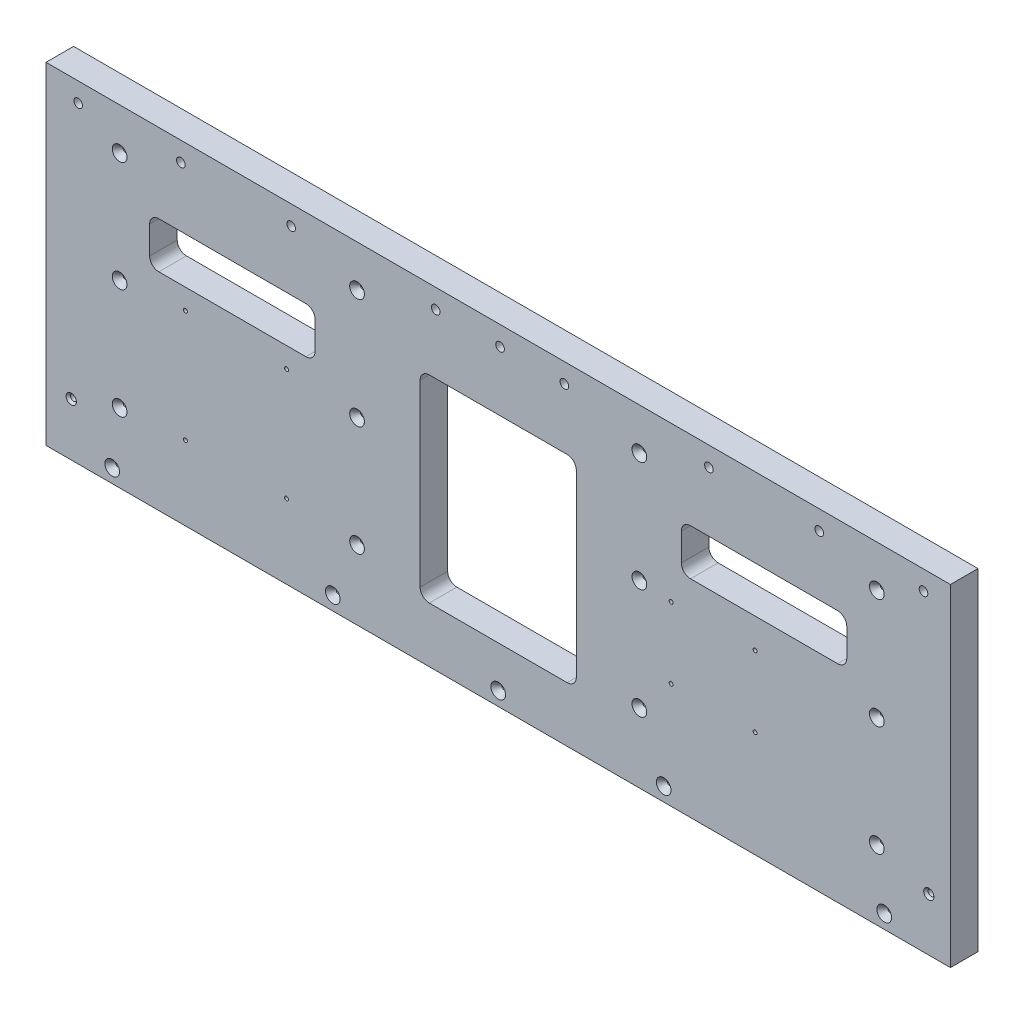
SolidWorks part; units mm, degrees
material "MDF"
ref_plane "Front Plane" through (0, 0, 0) normal (0, 0, 1) x (1, 0, 0)
ref_plane "Top Plane" through (0, 0, 0) normal (0, 1, 0) x (1, 0, 0)
ref_plane "Right Plane" through (0, 0, 0) normal (1, 0, 0) x (0, 0, -1)
sketch "Sketch1" plane through (0, 0, 0) normal (0, 0, 1) x (1, 0, 0)
  line L0 (128.7463, -697.8385) -> (128.7463, -158.115) construction
  line L1 (-496.0937, -132.715) -> (128.7463, -132.715)
  line L2 (-496.0937, -132.715) -> (-496.0937, -361.95)
  line L3 (-496.0937, -361.95) -> (128.7463, -361.95)
  line L4 (128.7463, -132.715) -> (128.7463, -361.95)
  line L5 (-496.0937, -132.715) -> (-496.0937, -697.8385) construction
  line L12 (128.7463, -132.715) -> (-84.6137, -132.715) construction
  line L13 (-290.722, -342.9) -> (-271.672, -342.9) construction
  dimension "D1" = 19.05
extrude "Boss-Extrude1" add sketch "Sketch1" along normal blind 19.05
hole_wizard "5/64 (0.07813) Diameter Hole1" positions "Sketch5" profile "Sketch6" hole size "5/64" standard "ANSI Inch"
sketch "Sketch5" plane through (-182.4037, -6471.4599, 19.05) normal (0, 0, 1) x (1, 0, 0)
  line L1 (-1.27, 6109.5099) -> (-1.27, 6338.7449) construction
  point P0 (-262.8265, 6157.4524)
  point P6 (-98.7933, 6157.4524)
  point P18 (-262.8265, 6233.6524)
  point P19 (-98.7933, 6233.6524)
  point P22 (-262.8265, 6309.8524)
  point P23 (-98.7933, 6309.8524)
  point P24 (-267.97, 6119.0349)
  point P34 (-115.57, 6119.0349)
  point P37 (-1.27, 6119.0349)
  point P40 (113.03, 6119.0349)
  point P44 (265.43, 6119.0349)
  point P55 (96.2533, 6309.8524)
  point P56 (260.2865, 6309.8524)
  point P59 (96.2533, 6233.6524)
  point P60 (260.2865, 6233.6524)
  point P63 (96.2533, 6157.4524)
  point P64 (260.2865, 6157.4524)
sketch "Sketch6" plane through (-445.2302, -314.0075, 19.05) normal (1, 0, 0) x (0, -1, 0)
  line L0 (0, 0) -> (0, 39.0539)
  line L1 (0, 39.0539) -> (1.5875, 38.1)
  line L2 (1.5875, 38.1) -> (1.5875, 4.0177)
  line L3 (1.5875, 4.0177) -> (5.08, 0)
  line L4 (5.08, 0) -> (0, 0)
  line L5 (-1.5875, 4.0177) -> (-5.08, 0) construction
  line L6 (0, 39.0539) -> (-1.5875, 38.1) construction
  line L7 (0, -6.35) -> (0, 107.95) construction
  dimension "Hole Dia." = 3.175
  dimension "Hole Depth" = 38.1
  dimension "Near C'Sink Dia." = 10.16
  dimension "Near C'Sink Angle" = 82
  dimension "Drill Angle" = 118
hole_wizard "15/64 (0.23438) Diameter Hole1" positions "Sketch7" profile "Sketch8" hole size "15/64" standard "ANSI Inch" end condition up to next
sketch "Sketch7" plane through (0, 0, 0) normal (0, 0, -1) x (-1, 0, 0)
  point P0 (402.9075, -146.05)
  point P2 (326.7075, -146.05)
  point P4 (226.8537, -146.05)
  point P6 (182.4037, -146.05)
  point P8 (137.9537, -146.05)
  point P10 (38.1, -146.05)
  point P12 (-38.1, -146.05)
  point P13 (473.8687, -146.05)
  point P17 (-110.1471, -146.05)
sketch "Sketch8" plane through (-402.9075, -146.05, 0) normal (1, 0, 0) x (0, 1, 0)
  line L0 (0, 0) -> (0, 19.05)
  line L1 (0, 19.05) -> (2.9766, 19.05)
  line L2 (2.9766, 19.05) -> (2.9766, 0)
  line L5 (2.9766, 0) -> (0, 0)
  line L11 (0, -6.35) -> (0, 107.95) construction
  dimension "Thru Hole Dia." = 5.9533
  dimension "Thru Hole Depth" = 19.05
sketch "Sketch9" plane through (0, 0, 0) normal (0, 0, -1) x (-1, 0, 0)
  line L0 (0, -157.1498) -> (0, -342.9) construction
  line L1 (0, -250.0249) -> (93.1355, -250.0249) construction
  line L2 (61.3728, -330.2) -> (-61.3728, -330.2)
  line L3 (61.3728, -330.2) -> (61.3728, -169.8498)
  line L4 (61.3728, -169.8498) -> (-61.3728, -169.8498)
  line L5 (-61.3728, -330.2) -> (-61.3728, -169.8498)
  line L6 (61.3728, -330.2) -> (-61.3728, -169.8498) construction
  line L7 (61.3728, -169.8498) -> (-61.3728, -330.2) construction
  line L8 (93.1355, -250.0249) -> (271.672, -250.0249) construction
  line L9 (364.8075, -157.1625) -> (364.8075, -342.9) construction
  line L10 (258.972, -330.2) -> (105.8355, -330.2)
  line L11 (258.972, -330.2) -> (258.972, -169.8498)
  line L12 (258.972, -169.8498) -> (105.8355, -169.8498)
  line L13 (105.8355, -330.2) -> (105.8355, -169.8498)
  line L14 (258.972, -330.2) -> (105.8355, -169.8498) construction
  line L15 (258.972, -169.8498) -> (105.8355, -330.2) construction
  line L17 (426.1802, -330.2127) -> (303.4347, -330.2127)
  line L18 (426.1802, -330.2127) -> (426.1802, -169.8498)
  line L19 (426.1802, -169.8498) -> (303.4347, -169.8498)
  line L20 (303.4347, -330.2127) -> (303.4347, -169.8498)
  line L21 (426.1802, -330.2127) -> (303.4347, -169.8498) construction
  line L22 (426.1802, -169.8498) -> (303.4347, -330.2127) construction
  point P3 (0, -250.0249)
  point P8 (-74.0728, -342.9)
  point P13 (182.4037, -250.0249)
  point P20 (364.8075, -250.0313)
  dimension "D1" = 12.7
  dimension "D2" = 12.7
  dimension "D3" = 12.7
extrude "Cut-Extrude1" [suppressed] cut sketch "Sketch9" against normal up to next
fillet "Fillet1" [suppressed] radius 12.7
hole_wizard "#2 Clearance Hole1" positions "Sketch10" profile "Sketch11" hole size "#2" standard "ANSI Inch" end condition up to next
sketch "Sketch10" plane through (0, 0, 19.05) normal (0, 0, 1) x (1, 0, 0)
  point P2 (-6.2354, -239.6)
  point P4 (-64.2354, -239.6)
  point P6 (-64.2354, -288.6)
  point P8 (-6.2354, -288.6)
sketch "Sketch11" plane through (-6.2354, -239.6, 19.05) normal (1, 0, 0) x (0, -1, 0)
  line L0 (0, 0) -> (0, 19.05)
  line L1 (0, 19.05) -> (1.3525, 19.05)
  line L2 (1.3525, 19.05) -> (1.3525, 0)
  line L5 (1.3525, 0) -> (0, 0)
  line L11 (0, -6.35) -> (0, 107.95) construction
  dimension "Thru Hole Dia." = 2.7051
  dimension "Thru Hole Depth" = 19.05
hole_wizard "#2 Clearance Hole2" positions "Sketch12" profile "Sketch13" hole size "#2" standard "ANSI Inch" end condition up to next
sketch "Sketch12" plane through (0, 0, 0) normal (0, 0, -1) x (-1, 0, 0)
  point P0 (399.7261, -233.172)
  point P2 (329.8761, -233.172)
  point P4 (329.8761, -310.642)
  point P6 (399.7261, -310.642)
sketch "Sketch13" plane through (-399.7261, -233.172, 0) normal (1, 0, 0) x (0, 1, 0)
  line L0 (0, 0) -> (0, 19.05)
  line L1 (0, 19.05) -> (1.3525, 19.05)
  line L2 (1.3525, 19.05) -> (1.3525, 0)
  line L5 (1.3525, 0) -> (0, 0)
  line L11 (0, -6.35) -> (0, 107.95) construction
  dimension "Thru Hole Dia." = 2.7051
  dimension "Thru Hole Depth" = 19.05
hole_wizard "CSK for #6 Flat Head Machine Screw (100)1" positions "Sketch16" profile "Sketch17" countersink size "#6" standard "ANSI Inch" end condition up to next
sketch "Sketch16" plane through (0, 0, 19.05) normal (0, 0, 1) x (1, 0, 0)
  point P6 (113.8236, -325.4344)
  point P8 (-478.6312, -325.4375)
sketch "Sketch17" plane through (113.8236, -325.4344, 19.05) normal (1, 0, 0) x (0, -1, 0)
  line L0 (0, 0) -> (0, 19.05)
  line L1 (0, 19.05) -> (2.1526, 19.05)
  line L2 (2.1526, 19.05) -> (2.1526, 1.5998)
  line L3 (2.1526, 1.5998) -> (3.5433, 0)
  line L5 (3.5433, 0) -> (0, 0)
  line L6 (-2.1526, 1.5998) -> (-3.5433, 0) construction
  line L11 (0, -6.35) -> (0, 107.95) construction
  dimension "Thru Hole Dia." = 4.3053
  dimension "Thru Hole Depth" = 19.05
  dimension "Near C'Sink Dia." = 7.0866
  dimension "Near C'Sink Angle" = 82
sketch "Sketch18" plane through (0, 0, 0) normal (0, 0, -1) x (-1, 0, 0)
  line L0 (-74.0728, -171.45) -> (74.0855, -171.45) construction
  line L1 (-57.1437, -187.325) -> (57.1563, -187.325)
  line L2 (-57.1437, -187.325) -> (-57.1437, -219.075)
  line L3 (-57.1437, -219.075) -> (57.1563, -219.075)
  line L4 (57.1563, -187.325) -> (57.1563, -219.075)
  line L5 (-57.1437, -187.325) -> (57.1563, -219.075) construction
  line L6 (-57.1437, -219.075) -> (57.1563, -187.325) construction
  line L7 (496.0937, -361.95) -> (-128.7463, -361.95) construction
  line L8 (183.6737, -361.95) -> (183.6737, -132.715) construction
  line L9 (-128.7463, -132.715) -> (496.0937, -132.715) construction
  line L10 (424.4911, -187.325) -> (424.4911, -219.075)
  line L11 (424.4911, -219.075) -> (310.1911, -219.075)
  line L12 (310.1911, -187.325) -> (310.1911, -219.075)
  line L13 (424.4911, -187.325) -> (310.1911, -187.325)
  line L15 (237.6487, -323.85) -> (129.6987, -323.85)
  line L16 (237.6487, -323.85) -> (237.6487, -187.325)
  line L17 (237.6487, -187.325) -> (129.6987, -187.325)
  line L18 (129.6987, -323.85) -> (129.6987, -187.325)
  line L19 (237.6487, -323.85) -> (129.6987, -187.325) construction
  line L20 (237.6487, -187.325) -> (129.6987, -323.85) construction
  point P4 (0.0063, -203.2)
  point P8 (0.0063, -171.45)
  point P19 (183.6737, -255.5875)
  dimension "D1" = 114.3
  dimension "D2" = 31.75
  dimension "D3" = 158.75
  dimension "D4" = 38.1
  dimension "D6" = 107.95
extrude "Cut-Extrude2" cut sketch "Sketch18" against normal up to next
fillet "Fillet2" radius 6.35 12 edges at (-310.1911, -187.325, 9.525) (-310.1911, -219.075, 9.525) (-424.4911, -219.075, 9.525) (-424.4911, -187.325, 9.525) (-237.6487, -187.325, 9.525) (-237.6487, -323.85, 9.525) (-129.6987, -323.85, 9.525) (-129.6987, -187.325, 9.525) (-57.1563, -187.325, 9.525) (-57.1563, -219.075, 9.525) (57.1437, -219.075, 9.525) (57.1437, -187.325, 9.525)
